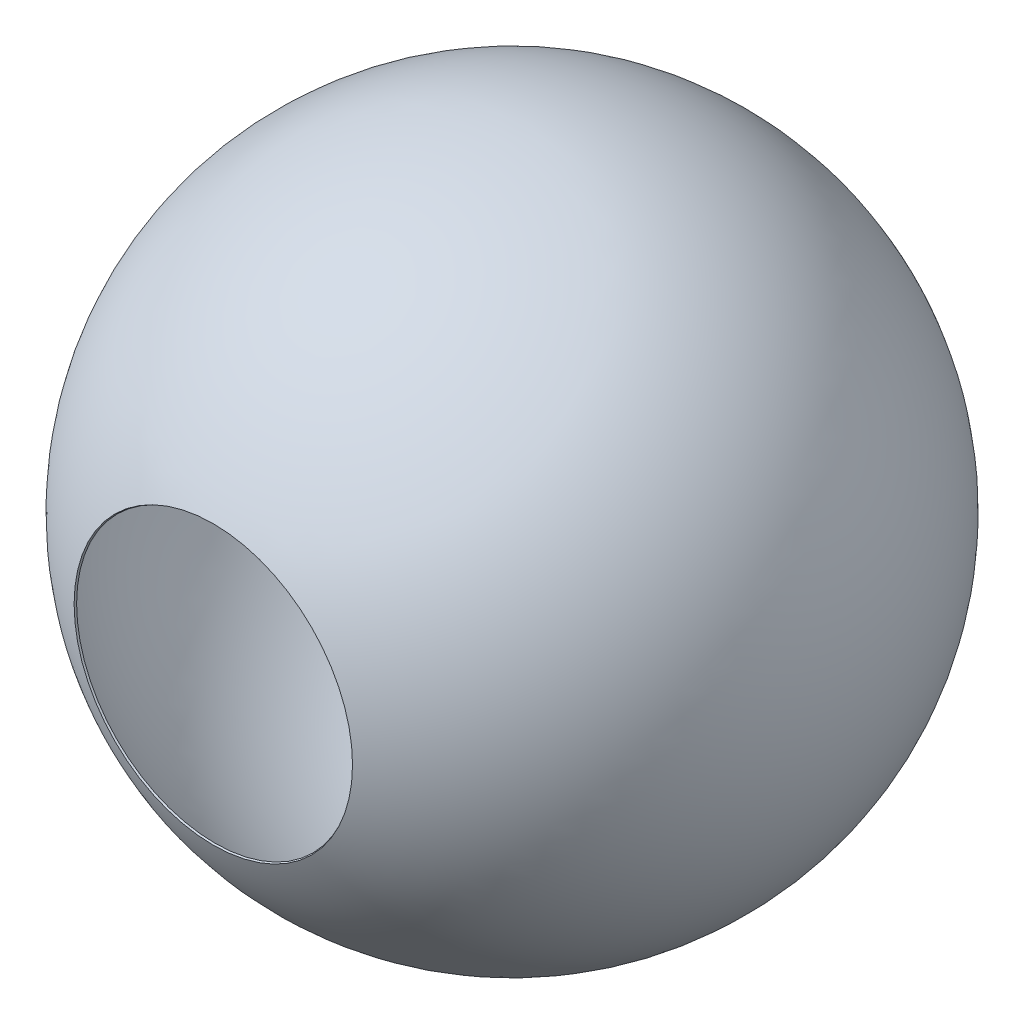
SolidWorks part; units mm, degrees
ref_plane "Front Plane" through (0, 0, 0) normal (0, 0, 1) x (1, 0, 0)
ref_plane "Top Plane" through (0, 0, 0) normal (0, 1, 0) x (1, 0, 0)
ref_plane "Right Plane" through (0, 0, 0) normal (1, 0, 0) x (0, 0, -1)
sketch "Sketch1" plane through (0, 0, 0) normal (1, 0, 0) x (0, 0, -1)
  line L0 (528.5016, 124.6399) -> (528.5016, 0)
  line L3 (-495, 230.6517) -> (-495, 0) construction
  line L4 (-492.1901, 229.3424) -> (0, 0) construction
  line L5 (-495, 230.6517) -> (-492.1901, 229.3424)
  line L6 (-495, 0) -> (531.6016, 0) construction
  line L7 (531.6016, 125) -> (531.6016, 0)
  line L8 (528.5016, 0) -> (531.6016, 0)
  arc A0 (531.6016, 125) -> (-495, 230.6517) centre (0, 0) ccw
  arc A1 (528.5016, 124.6399) -> (-492.1901, 229.3424) centre (0, 0) ccw
  dimension "D2" = 543
  dimension "D3" = 495
  dimension "D4" = 125
  dimension "D5" = 3.1
  dimension "PressureHull_InnerRadius" = 546.1
revolve "Shell" add sketch "Sketch1" angle 360 about L6
sketch "Sketch3" plane through (0, 0, 0) normal (0, 0, 1) x (1, 0, 0)
  line L0 (-356.5753, -20.7815) -> (269.657, 26.3052) construction
  line L1 (0, 543) -> (0, -543) construction
  line L2 (0, 0) -> (271.5, 470.2518) construction
  line L3 (0, 0) -> (-271.5, 470.2518) construction
  line L4 (-543, 0) -> (543, 0) construction
  line L5 (0, 0) -> (457.9616, -291.7537) construction
  line L6 (0, 0) -> (-457.9616, -291.7537) construction
  circle A0 centre (0, 0) radius 543
  dimension "D1" = 1086
  dimension "D2" = 60
  dimension "D3" = 115
equation "\"PressureHull_InnerRadius\"= 546.1mm"
equation "\"PressureHull_OuterRadius\"= 609.6mm"
equation "\"InnerShell_InnerRadius\"= 543mm"
